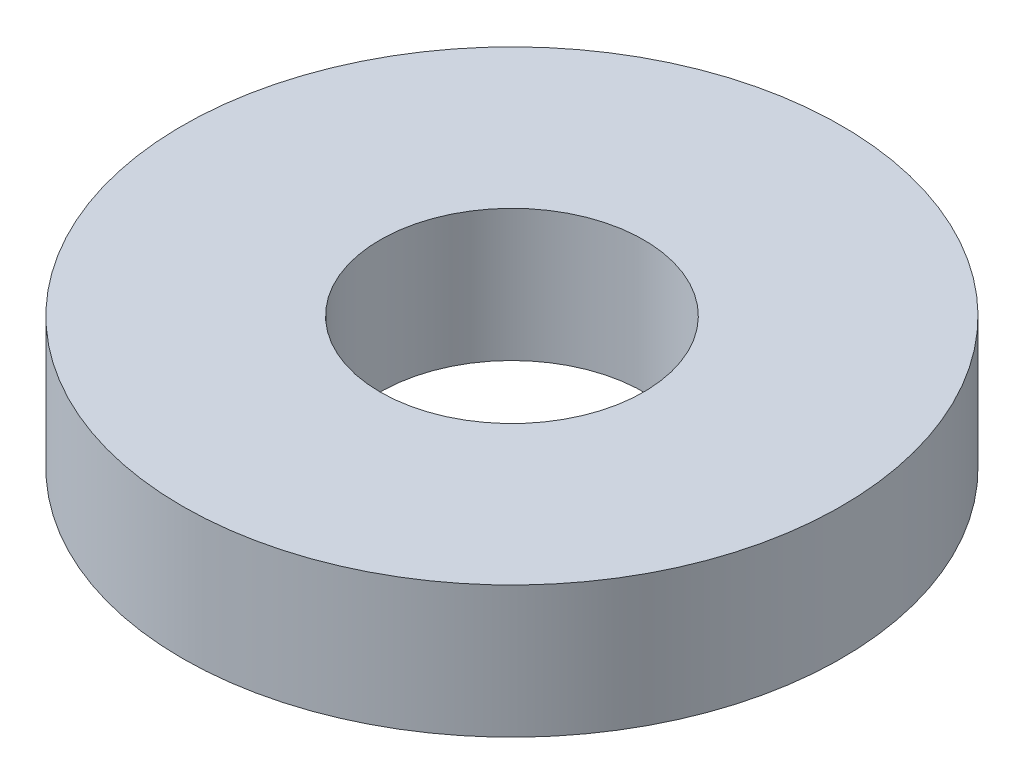
SolidWorks part; units mm, degrees
ref_plane "Front Plane" through (0, 0, 0) normal (0, 0, 1) x (1, 0, 0)
ref_plane "Top Plane" through (0, 0, 0) normal (0, 1, 0) x (1, 0, 0)
ref_plane "Right Plane" through (0, 0, 0) normal (1, 0, 0) x (0, 0, -1)
sketch "Sketch1" plane through (0, 0, 0) normal (0, 1, 0) x (1, 0, 0)
  circle A0 centre (0, 0) radius 50
  dimension "FLANGE_OD" = 100
extrude "Boss-Extrude1" add sketch "Sketch1" along normal blind 20
sketch "Sketch2" plane through (0, 0, 0) normal (0, 1, 0) x (1, 0, 0)
  circle A0 centre (0, 0) radius 20
  dimension "BORE_D" = 40
extrude "Cut-Extrude1" cut sketch "Sketch2" along normal through all
sketch "Sketch3" plane through (0, 20, 0) normal (0, 1, 0) x (1, 0, 0)
  circle A0 centre (0, 0) radius 14.1684 construction
  circle A1 centre (-14.1684, 0) radius 2.5448
  dimension "BOLT_D" = 5.0896
  dimension "BOLT_PCD" = 28.3368
extrude "Cut-Extrude2" cut sketch "Sketch3" against normal blind 19.8375 rebuild error yes
pattern_circular "CirPattern1" count 6 over 360 rebuild error yes
